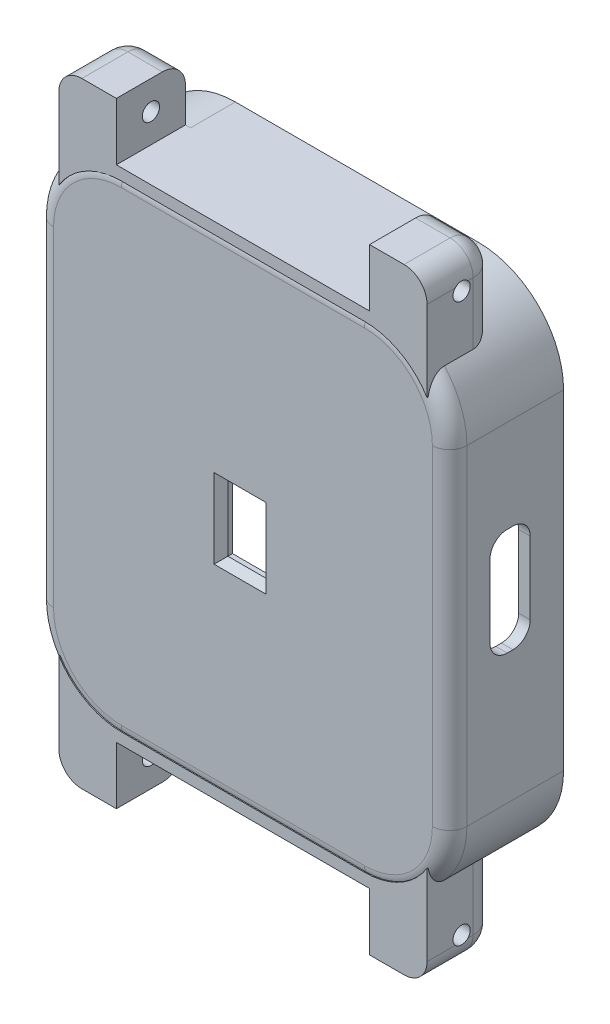
SolidWorks part; units mm, degrees
other "相机1"
ref_plane "前视基准面" through (0, 0, 0) normal (0, 0, 1) x (1, 0, 0)
ref_plane "上视基准面" through (0, 0, 0) normal (0, 1, 0) x (1, 0, 0)
ref_plane "右视基准面" through (0, 0, 0) normal (1, 0, 0) x (0, 0, -1)
sketch "草图1" plane through (0, 0, 0) normal (0, 0, 1) x (1, 0, 0)
  line L0 (-10.56, 20.73) -> (10.56, 20.73)
  line L1 (-10.56, 21.73) -> (10.56, 21.73)
  line L2 (-17.96, 14.33) -> (-17.96, -14.33)
  line L3 (-10.56, -21.73) -> (10.56, -21.73)
  line L4 (17.96, 14.33) -> (17.96, -14.33)
  line L5 (-17.96, 21.73) -> (17.96, -21.73) construction
  line L6 (-17.96, -21.73) -> (17.96, 21.73) construction
  line L7 (16.96, 14.33) -> (16.96, -14.33)
  line L8 (-10.56, -20.73) -> (10.56, -20.73)
  line L9 (-16.96, 14.33) -> (-16.96, -14.33)
  line L10 (-16.21, 14.82) -> (-11.21, 19.82)
  line L11 (-1.91, 2.22) -> (1.39, 2.22)
  line L12 (-1.91, 2.22) -> (-1.91, -3.48)
  line L13 (-1.91, -3.48) -> (1.39, -3.48)
  line L14 (1.39, 2.22) -> (1.39, -3.48)
  line L15 (-11.21, 19.82) -> (11.09, 19.82)
  line L16 (-16.21, 14.82) -> (-16.21, -14.48)
  line L17 (-11.21, -19.48) -> (11.09, -19.48)
  line L18 (16.09, 14.82) -> (16.09, -14.48)
  line L19 (11.09, 19.82) -> (16.09, 14.82)
  line L20 (11.09, -19.48) -> (16.09, -14.48)
  line L21 (-16.21, -14.48) -> (-11.21, -19.48)
  line L22 (16.09, 14.82) -> (16.96, 14.82)
  line L23 (-6.21, 19.82) -> (16.09, 19.82)
  line L24 (-6.21, 19.82) -> (-6.21, 8.42)
  line L25 (-6.21, 8.42) -> (16.09, 8.42)
  line L26 (16.09, 19.82) -> (16.09, 8.42)
  line L27 (16.09, 5.77) -> (17.59, 5.77)
  line L28 (16.09, 5.77) -> (16.09, -3.23)
  line L29 (16.09, -3.23) -> (17.59, -3.23)
  line L30 (17.59, 5.77) -> (17.59, -3.23)
  line L31 (-16.21, 13.32) -> (-16.91, 13.32)
  line L32 (-16.21, 13.32) -> (-16.21, 10.82)
  line L33 (-16.21, 10.82) -> (-16.91, 10.82)
  line L34 (-16.91, 13.32) -> (-16.91, 10.82)
  line L35 (-16.96, -10.73) -> (-11.96, -10.73)
  line L36 (-16.96, -10.73) -> (-16.96, -13.73)
  line L37 (-16.96, -13.73) -> (-11.96, -13.73)
  line L38 (-11.96, -10.73) -> (-11.96, -13.73)
  line L43 (16.96, -10.73) -> (11.96, -10.73)
  line L44 (16.96, -10.73) -> (16.96, -13.73)
  line L45 (16.96, -13.73) -> (11.96, -13.73)
  line L46 (11.96, -10.73) -> (11.96, -13.73)
  line L47 (-16.96, 7.73) -> (-11.96, 7.73)
  line L48 (-16.96, 7.73) -> (-16.96, 4.73)
  line L49 (-16.96, 4.73) -> (-11.96, 4.73)
  line L50 (-11.96, 7.73) -> (-11.96, 4.73)
  line L51 (11.96, 8.42) -> (16.96, 8.42)
  line L52 (11.96, 8.42) -> (11.96, 6.02)
  line L53 (11.96, 6.02) -> (16.96, 6.02)
  line L54 (16.96, 8.42) -> (16.96, 6.02)
  line L55 (-16.21, 14.82) -> (-16.96, 14.82)
  line L56 (11.09, 19.82) -> (13.8494, 19.82)
  line L57 (-11.21, 19.82) -> (-13.8494, 19.82)
  line L58 (-11.21, -19.48) -> (-14.3597, -19.48)
  line L59 (11.09, -19.48) -> (14.3597, -19.48)
  arc A0 (-17.96, -14.33) -> (-10.56, -21.73) centre (-10.56, -14.33) ccw
  arc A1 (10.56, -21.73) -> (17.96, -14.33) centre (10.56, -14.33) ccw
  arc A2 (10.56, 21.73) -> (17.96, 14.33) centre (10.56, 14.33) cw
  arc A3 (-10.56, 21.73) -> (-17.96, 14.33) centre (-10.56, 14.33) ccw
  arc A4 (10.56, 20.73) -> (16.96, 14.33) centre (10.56, 14.33) cw
  arc A5 (10.56, -20.73) -> (16.96, -14.33) centre (10.56, -14.33) ccw
  arc A6 (-16.96, -14.33) -> (-10.56, -20.73) centre (-10.56, -14.33) ccw
  arc A7 (-10.56, 20.73) -> (-16.96, 14.33) centre (-10.56, 14.33) ccw
  point P0 (0, 0)
  point P34 (-16.21, 19.82)
  point P35 (16.09, -19.48)
  point P36 (-16.21, -19.48)
  point P37 (16.09, 19.82)
  dimension "D3" = 7.4
  dimension "D1" = 35.92
  dimension "D2" = 43.46
  dimension "D5" = 3.3
  dimension "D6" = 5.7
  dimension "D7" = 32.3
  dimension "D8" = 39.3
  dimension "D9" = 16
  dimension "D10" = 14.3
  dimension "D11" = 11.4
  dimension "D12" = 22.3
  dimension "D13" = 1.5
  dimension "D14" = 9
  dimension "D19" = 16.25
  dimension "D20" = 0.75
  dimension "D21" = 1.25
  dimension "D22" = 0.7
  dimension "D23" = 2.5
  dimension "D24" = 9
  dimension "D25" = 5
  dimension "D26" = 5
  dimension "D27" = 3
  dimension "D28" = 3
  dimension "D29" = 7
  dimension "D30" = 7
  dimension "D31" = 5
  dimension "D32" = 3
  dimension "D33" = 16
  dimension "D35" = 5
  dimension "D4" = 1
extrude "凸台-拉伸1" add sketch "草图1" against normal blind 1 contours A3 L2 A0 L3 A1 L4 A2 L1
extrude "凸台-拉伸2" add sketch "草图1<3>" against normal blind 9.9 contours L7 A5 L8 A6 L9 A7 L0 A4 | L4 A1 L3 A0 L2 A3 L1 A2
sketch "草图1<3>" plane through (0, 0, 0) normal (0, 0, 1) x (1, 0, 0) same geometry as "草图1"
extrude "凸台-拉伸3" add sketch "草图1<4>" against normal blind 2.5 contours L43 L46 L45 L44 | L38 L37 L36 L35 | L50 L49 L48 L47 | L52 L53 L54 L51
sketch "草图1<4>" plane through (0, 0, 0) normal (0, 0, 1) x (1, 0, 0) same geometry as "草图1"
extrude "切除-拉伸1" cut sketch "草图1<6>" against normal blind 4 contours L14 L11 L12 L13 region at (-0.26, -0.63, 0)
sketch "草图1<6>" plane through (0, 0, 0) normal (0, 0, 1) x (1, 0, 0) same geometry as "草图1"
extrude "凸台-拉伸5" add sketch "草图1<8>" against normal blind 4 contours L51 L18 L27 L7 | L45 L7 L43 L18 | L9 L37 L16 L35 | L9 L49 L16 L47 region at (-16.585, 6.23, 0) region at (16.525, 7.22, 0) region at (-16.585, -12.23, 0) region at (16.525, -12.23, 0)
sketch "草图1<8>" plane through (0, 0, 0) normal (0, 0, 1) x (1, 0, 0) same geometry as "草图1"
sketch "草图2" plane through (0, 0, -1) normal (0, 0, -1) x (-1, 0, 0)
  line L0 (-15.6, 14.47) -> (-10.6, 19.47)
  line L1 (-10.6, -19.47) -> (10.6, -19.47)
  line L2 (-15.6, -14.47) -> (-15.6, 14.47)
  line L3 (-10.6, 19.47) -> (10.6, 19.47)
  line L4 (15.6, -14.47) -> (15.6, 14.47)
  line L5 (-15.6, -19.47) -> (15.6, 19.47) construction
  line L6 (-15.6, 19.47) -> (15.6, -19.47) construction
  line L7 (10.6, 19.47) -> (15.6, 14.47)
  line L8 (10.6, -19.47) -> (15.6, -14.47)
  line L9 (-15.6, -14.47) -> (-10.6, -19.47)
  line L11 (6.21, 8.42) -> (-16.09, 8.42)
  line L12 (6.21, 8.42) -> (6.21, 19.82)
  line L13 (6.21, 19.82) -> (-16.09, 19.82)
  line L14 (-16.09, 8.42) -> (-16.09, 19.82)
  point P0 (0, 0)
  line M14 (-16.96, 8.42) -> (-11.96, 8.42)
  dimension "D1" = 31.2
  dimension "D2" = 38.94
extrude "切除-拉伸2" cut sketch "草图2" against normal blind 0.5 contours L12 L13 L0 L2 L11 M14 region at (4.1896, 13.7339, -1)
sketch "草图3" plane through (-17.96, 0, 0) normal (-1, 0, 0) x (0, 0, 1)
  line L1 (0, 0) -> (-9.9, 0)
  line L2 (0, 0) -> (0, 21.73)
  line L3 (0, 21.73) -> (-9.9, 21.73)
  line L4 (-9.9, 0) -> (-9.9, 21.73)
  line L5 (0, 0) -> (-9.9, 0)
  line L6 (0, 0) -> (0, -21.73)
  line L7 (0, -21.73) -> (-9.9, -21.73)
  line L8 (-9.9, 0) -> (-9.9, -21.73)
  line L13 (0, 12.67) -> (-9.9, 12.67)
  line L14 (0, 10.17) -> (-9.9, 10.17)
  line L15 (-5.5, 14.42) -> (-4.5, 14.42)
  line L16 (-7, 12.92) -> (-7, 9.92)
  line L17 (-5.5, 8.42) -> (-4.5, 8.42)
  line L18 (-3, 12.92) -> (-3, 9.92)
  arc A0 (-4.5, 8.42) -> (-3, 9.92) centre (-4.5, 9.92) ccw
  arc A1 (-4.5, 14.42) -> (-3, 12.92) centre (-4.5, 12.92) cw
  arc A2 (-7, 9.92) -> (-5.5, 8.42) centre (-5.5, 9.92) ccw
  arc A3 (-5.5, 14.42) -> (-7, 12.92) centre (-5.5, 12.92) ccw
  point P21 (-3, 8.42)
  point P24 (-3, 14.42)
  point P27 (-7, 8.42)
  point P30 (-7, 14.42)
  line M11 (0, 14.33) -> (-9.9, 14.33)
  dimension "D7" = 1.5
  dimension "D1" = 3
  dimension "D2" = 6
  dimension "D3" = 1.75
  dimension "D4" = 2.5
  dimension "D5" = 11.56
  dimension "D6" = 4
  dimension "D8" = 10.91
extrude "切除-拉伸3" cut sketch "草图3" against normal blind 10 contours L18 L13 L16 L14 | L15 A3 L16 L13 L18 A1 | L16 A2 L17 A0 L18 L14 | L15 A3 A1 M11 region at (-17.96, 9.3814, -5) region at (-17.96, 11.42, -5) region at (-17.96, 13.435, -5) region at (-17.96, 14.3714, -5)
sketch "草图4" plane through (17.96, 0, 0) normal (1, 0, 0) x (0, 0, -1)
  line L0 (3.5, 21.73) -> (3.5, -21.73)
  line L1 (0, 0) -> (9.9, 0)
  line L2 (0, 0) -> (0, -21.73)
  line L3 (0, -21.73) -> (9.9, -21.73)
  line L4 (9.9, 0) -> (9.9, -21.73)
  line L5 (0, 0) -> (9.9, 0)
  line L6 (0, 0) -> (0, 21.73)
  line L7 (0, 21.73) -> (9.9, 21.73)
  line L8 (9.9, 0) -> (9.9, 21.73)
  line L10 (5, 6.27) -> (5.5, 6.27)
  line L11 (3.5, 4.77) -> (3.5, -1.53)
  line L12 (5, -3.03) -> (5.5, -3.03)
  line L13 (7, 4.77) -> (7, -1.53)
  arc A0 (5.5, -3.03) -> (7, -1.53) centre (5.5, -1.53) ccw
  arc A1 (3.5, -1.53) -> (5, -3.03) centre (5, -1.53) ccw
  arc A2 (5.5, 6.27) -> (7, 4.77) centre (5.5, 4.77) cw
  arc A3 (5, 6.27) -> (3.5, 4.77) centre (5, 4.77) ccw
  point P17 (7, -3.03)
  point P22 (7, 6.27)
  point P25 (3.5, 6.27)
  dimension "D5" = 1.5
  dimension "D1" = 3.5
  dimension "D2" = 3.5
  dimension "D3" = 9.3
  dimension "D4" = 28
extrude "切除-拉伸4" cut sketch "草图4" against normal blind 10 contours L10 A3 L0 L1 L13 A2 | L0 A1 L12 A0 L13 L1 region at (17.96, 3.0061, -5.25) region at (17.96, -1.3968, -5.25)
extrude "凸台-拉伸6" add sketch "草图1<13>" against normal blind 9.9 contours L0 A7 L57 L15 L23 A4 | L58 A6 L8 A5 L59 L17 region at (0, 20.2596, 0) region at (0, -20.0813, 0)
sketch "草图1<13>" plane through (0, 0, 0) normal (0, 0, 1) x (1, 0, 0) same geometry as "草图1"
fillet "圆角1" radius 1.5 8 edges at (-15.7926, 19.5626, 0) (-17.96, 0, 0) (-15.7926, -19.5626, 0) (0, -21.73, 0) (15.7926, -19.5626, 0) (17.96, 0, 0) (15.7926, 19.5626, 0) (0, 21.73, 0)
sketch "草图5" plane through (0, 0, 0) normal (0, 0, 1) x (1, 0, 0)
  line L0 (16, 20.73) -> (16, 17.7014)
  line L1 (-17.96, 21.73) -> (17.96, 21.73)
  line L2 (-17.96, 21.73) -> (-17.96, -21.73)
  line L3 (-17.96, -21.73) -> (17.96, -21.73)
  line L4 (17.96, 21.73) -> (17.96, -21.73)
  line L5 (-17.96, 21.73) -> (17.96, -21.73) construction
  line L6 (-17.96, -21.73) -> (17.96, 21.73) construction
  line L11 (-16.9052, 20.4538) -> (16.9052, -20.4538) construction
  line L12 (-16.9052, -20.4538) -> (16.9052, 20.4538) construction
  line L13 (-10.56, 20.73) -> (10.56, 20.73)
  line L14 (-16.96, 14.33) -> (-16.96, -14.33)
  line L15 (-10.56, -20.73) -> (10.56, -20.73)
  line L16 (16.96, 14.33) -> (16.96, -14.33)
  line L17 (-16.96, 20.73) -> (16.96, -20.73) construction
  line L18 (-16.96, -20.73) -> (16.96, 20.73) construction
  line L19 (-16, 20.73) -> (-11, 20.73)
  line L20 (-16, 20.73) -> (-16, 24.73)
  line L21 (-14, 26.73) -> (-11, 26.73)
  line L22 (-11, 20.73) -> (-11, 26.73)
  line L23 (16, 20.73) -> (11, 20.73)
  line L24 (16, 20.73) -> (16, 24.73)
  line L25 (14, 26.73) -> (11, 26.73)
  line L26 (11, 20.73) -> (11, 26.73)
  line L27 (-16, 20.73) -> (-16, 17.7014)
  line L28 (-16.96, 0) -> (16.96, 0)
  line L29 (16, -20.73) -> (16, -17.7014)
  line L30 (-16, -20.73) -> (-16, -17.7014)
  line L31 (14, -26.73) -> (11, -26.73)
  line L32 (11, -20.73) -> (11, -26.73)
  line L33 (16, -20.73) -> (11, -20.73)
  line L34 (16, -20.73) -> (16, -24.73)
  line L35 (-14, -26.73) -> (-11, -26.73)
  line L36 (-11, -20.73) -> (-11, -26.73)
  line L37 (-16, -20.73) -> (-11, -20.73)
  line L38 (-16, -20.73) -> (-16, -24.73)
  arc A0 (10.56, -20.73) -> (16.96, -14.33) centre (10.56, -14.33) ccw
  arc A1 (-16.96, -14.33) -> (-10.56, -20.73) centre (-10.56, -14.33) ccw
  arc A2 (-10.56, 20.73) -> (-16.96, 14.33) centre (-10.56, 14.33) ccw
  arc A3 (10.56, 20.73) -> (16.96, 14.33) centre (10.56, 14.33) cw
  arc A4 (14, -26.73) -> (16, -24.73) centre (14, -24.73) ccw
  arc A5 (-14, -26.73) -> (-16, -24.73) centre (-14, -24.73) cw
  arc A6 (16, 24.73) -> (14, 26.73) centre (14, 24.73) ccw
  arc A7 (-16, 24.73) -> (-14, 26.73) centre (-14, 24.73) cw
  point P0 (0, 0)
  point P7 (0, 0)
  point P12 (0, 0)
  point P42 (0, 0)
  point P54 (16, -26.73)
  point P57 (-16, -26.73)
  point P60 (16, 26.73)
  point P63 (-16, 26.73)
  dimension "D9" = 6.4
  dimension "D10" = 2
  dimension "D1" = 33.92
  dimension "D2" = 41.46
  dimension "D3" = 22
  dimension "D4" = 6
  dimension "D5" = 6
  dimension "D6" = 1.96
  dimension "D7" = 1.96
  dimension "D8" = 5
extrude "凸台-拉伸7" add sketch "草图5" against normal blind 6 contours L24 A6 L25 L26 L1 | L26 L23 L24 L1 | A7 L20 L1 L22 L21 | L13 A3 L0 L23 L26 L1 L22 L19 L27 A2 | L19 L22 L1 L20 | L37 L38 L3 L36 | A5 L35 L36 L3 L38 | A1 L30 L37 L36 L3 L32 L33 L29 A0 L15 | L34 L33 L32 L3 | L31 A4 L34 L3 L32 region at (0, 20.8162, 0) region at (13.5, 21.23, 0) region at (13.427, 24.157, 0) region at (-13.5, 21.23, 0) region at (-13.427, 24.157, 0) region at (13.427, -24.157, 0) region at (13.5, -21.23, 0) region at (0, -20.8162, 0) region at (-13.427, -24.157, 0) region at (-13.5, -21.23, 0)
sketch "草图6" plane through (11, 0, 0) normal (-1, 0, 0) x (0, 0, 1)
  line L0 (-6, -21.73) -> (0, -26.73)
  line L1 (-6, -21.73) -> (0, -21.73)
  line L2 (-6, -21.73) -> (-6, -26.73)
  line L3 (-6, -26.73) -> (0, -26.73)
  line L4 (0, -21.73) -> (0, -26.73)
  line L5 (-6, -26.73) -> (0, -21.73)
  circle A0 centre (-3, -24.23) radius 0.75
  dimension "D1" = 1.5
extrude "切除-拉伸5" cut sketch "草图6" against normal through all and the other way through all contours L5 A0 L0 | L0 A0 L5 | L5 A0 L0 | L0 A0 L5 region at (11, -23.7915, -3) region at (11, -24.23, -3.4607) region at (11, -24.23, -2.5393) region at (11, -24.6685, -3)
sketch "草图7" plane through (11, 0, 0) normal (-1, 0, 0) x (0, 0, 1)
  line L0 (0, 26.73) -> (-6, 21.73)
  line L1 (0, 26.73) -> (-6, 26.73)
  line L2 (0, 26.73) -> (0, 21.73)
  line L3 (0, 21.73) -> (-6, 21.73)
  line L4 (-6, 26.73) -> (-6, 21.73)
  line L5 (0, 21.73) -> (-6, 26.73)
  circle A0 centre (-3, 24.23) radius 0.75
  dimension "D1" = 1.5
extrude "切除-拉伸6" cut sketch "草图7" against normal through all and the other way through all contours L0 A0 L5 | L5 A0 L0 | L0 A0 L5 | L5 A0 L0 region at (11, 24.23, -2.5393) region at (11, 24.6685, -3) region at (11, 23.7915, -3) region at (11, 24.23, -3.4607)
fillet "圆角2" radius 2 12 edges at (16, 22.0383, -6) (15.4142, 26.1442, -6) (-16, 22.0383, -6) (-15.4142, 26.1442, -6) (-16, -22.0383, -6) (-15.4142, -26.1442, -6) (16, -22.0383, -6) (15.4142, -26.1442, -6) (12.5, 26.73, -6) (-12.5, 26.73, -6) (-12.5, -26.73, -6) (12.5, -26.73, -6)
chamfer "倒角1" distance 0.6 angle 45 4 edges at (-0.26, -3.48, 0) (-1.91, -0.63, 0) (-0.26, 2.22, 0) (1.39, -0.63, 0)
